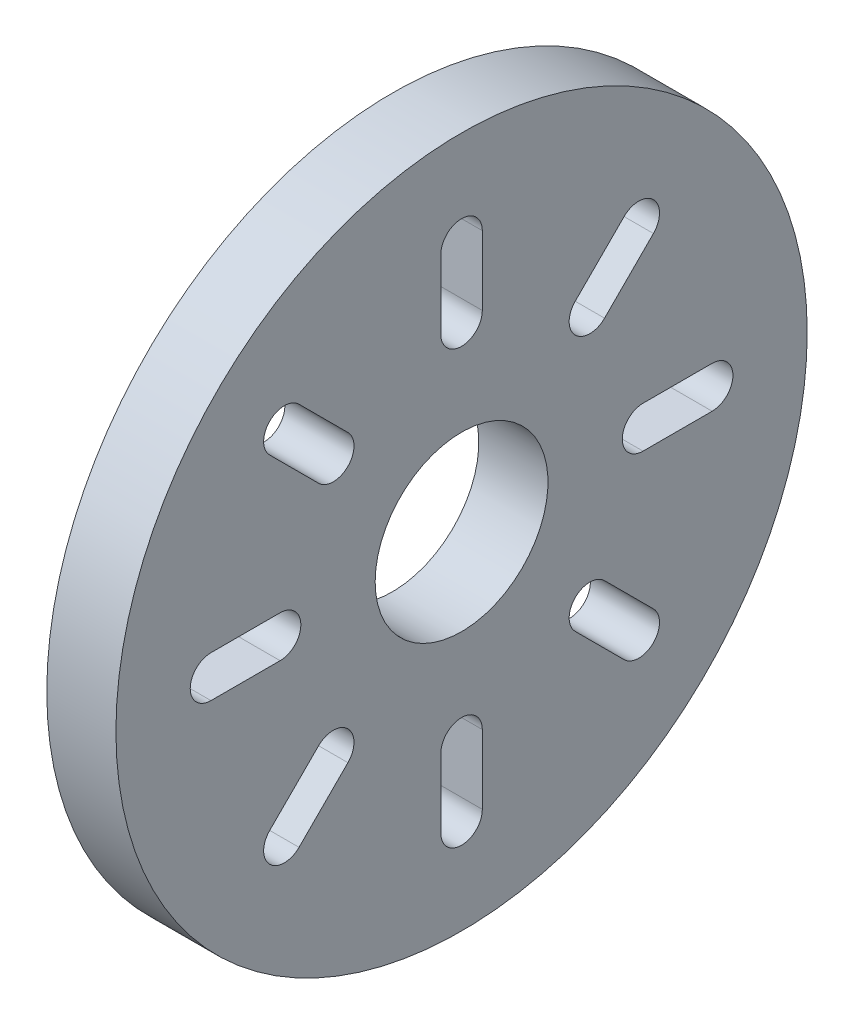
SolidWorks part; units mm, degrees
ref_plane "Front Plane" through (0, 0, 0) normal (0, 0, 1) x (1, 0, 0)
ref_plane "Top Plane" through (0, 0, 0) normal (0, 1, 0) x (1, 0, 0)
ref_plane "Right Plane" through (0, 0, 0) normal (1, 0, 0) x (0, 0, -1)
sketch "Sketch1" plane through (0, 0, 0) normal (1, 0, 0) x (0, 0, -1)
  line L0 (0, 36.25) -> (0, 26.25) construction
  line L1 (3, 36.25) -> (3, 26.25)
  line L2 (-3, 36.25) -> (-3, 26.25)
  line L3 (25.6326, 25.6326) -> (18.5616, 18.5616) construction
  line L4 (27.7539, 23.5113) -> (20.6829, 16.4402)
  line L5 (23.5113, 27.7539) -> (16.4402, 20.6829)
  line L6 (36.25, 0) -> (26.25, 0) construction
  line L7 (36.25, -3) -> (26.25, -3)
  line L8 (36.25, 3) -> (26.25, 3)
  line L9 (25.6326, -25.6326) -> (18.5616, -18.5616) construction
  line L10 (23.5113, -27.7539) -> (16.4402, -20.6829)
  line L11 (27.7539, -23.5113) -> (20.6829, -16.4402)
  line L12 (0, -36.25) -> (0, -26.25) construction
  line L13 (-3, -36.25) -> (-3, -26.25)
  line L14 (3, -36.25) -> (3, -26.25)
  line L15 (-25.6326, -25.6326) -> (-18.5616, -18.5616) construction
  line L16 (-27.7539, -23.5113) -> (-20.6829, -16.4402)
  line L17 (-23.5113, -27.7539) -> (-16.4402, -20.6829)
  line L18 (-36.25, 0) -> (-26.25, 0) construction
  line L19 (-36.25, 3) -> (-26.25, 3)
  line L20 (-36.25, -3) -> (-26.25, -3)
  line L21 (-25.6326, 25.6326) -> (-18.5616, 18.5616) construction
  line L22 (-23.5113, 27.7539) -> (-16.4402, 20.6829)
  line L23 (-27.7539, 23.5113) -> (-20.6829, 16.4402)
  circle A0 centre (0, 0) radius 50
  circle A1 centre (0, 0) radius 12.5
  arc A3 (3, 36.25) -> (-3, 36.25) centre (0, 36.25) ccw
  arc A4 (-3, 26.25) -> (3, 26.25) centre (0, 26.25) ccw
  arc A5 (27.7539, 23.5113) -> (23.5113, 27.7539) centre (25.6326, 25.6326) ccw
  arc A6 (16.4402, 20.6829) -> (20.6829, 16.4402) centre (18.5616, 18.5616) ccw
  arc A7 (36.25, -3) -> (36.25, 3) centre (36.25, 0) ccw
  arc A8 (26.25, 3) -> (26.25, -3) centre (26.25, 0) ccw
  arc A9 (23.5113, -27.7539) -> (27.7539, -23.5113) centre (25.6326, -25.6326) ccw
  arc A10 (20.6829, -16.4402) -> (16.4402, -20.6829) centre (18.5616, -18.5616) ccw
  arc A11 (-3, -36.25) -> (3, -36.25) centre (0, -36.25) ccw
  arc A12 (3, -26.25) -> (-3, -26.25) centre (0, -26.25) ccw
  arc A13 (-27.7539, -23.5113) -> (-23.5113, -27.7539) centre (-25.6326, -25.6326) ccw
  arc A14 (-16.4402, -20.6829) -> (-20.6829, -16.4402) centre (-18.5616, -18.5616) ccw
  arc A15 (-36.25, 3) -> (-36.25, -3) centre (-36.25, 0) ccw
  arc A16 (-26.25, -3) -> (-26.25, 3) centre (-26.25, 0) ccw
  arc A17 (-23.5113, 27.7539) -> (-27.7539, 23.5113) centre (-25.6326, 25.6326) ccw
  arc A18 (-20.6829, 16.4402) -> (-16.4402, 20.6829) centre (-18.5616, 18.5616) ccw
  point P4 (0, 0)
  point P7 (0, 31.25)
  point P15 (22.0971, 22.0971)
  point P22 (31.25, 0)
  point P29 (22.0971, -22.0971)
  point P36 (0, -31.25)
  point P43 (-22.0971, -22.0971)
  point P50 (-31.25, 0)
  point P57 (-22.0971, 22.0971)
  point P62 (0, 0)
  dimension "D1" = 100
  dimension "D2" = 25
  dimension "D3" = 3
  dimension "D4" = 3
  dimension "D5" = 3
  dimension "D6" = 10
  dimension "D8" = 10
  dimension "D9" = 10
  dimension "D7" = 8
extrude "Boss-Extrude2" add sketch "Sketch1" along normal blind 10 contours A0
extrude "Cut-Extrude2" cut sketch "Sketch1<4>" along normal blind 13 flip side to cut
sketch "Sketch1<4>" plane through (0, 0, 0) normal (1, 0, 0) x (0, 0, -1) same geometry as "Sketch1"
